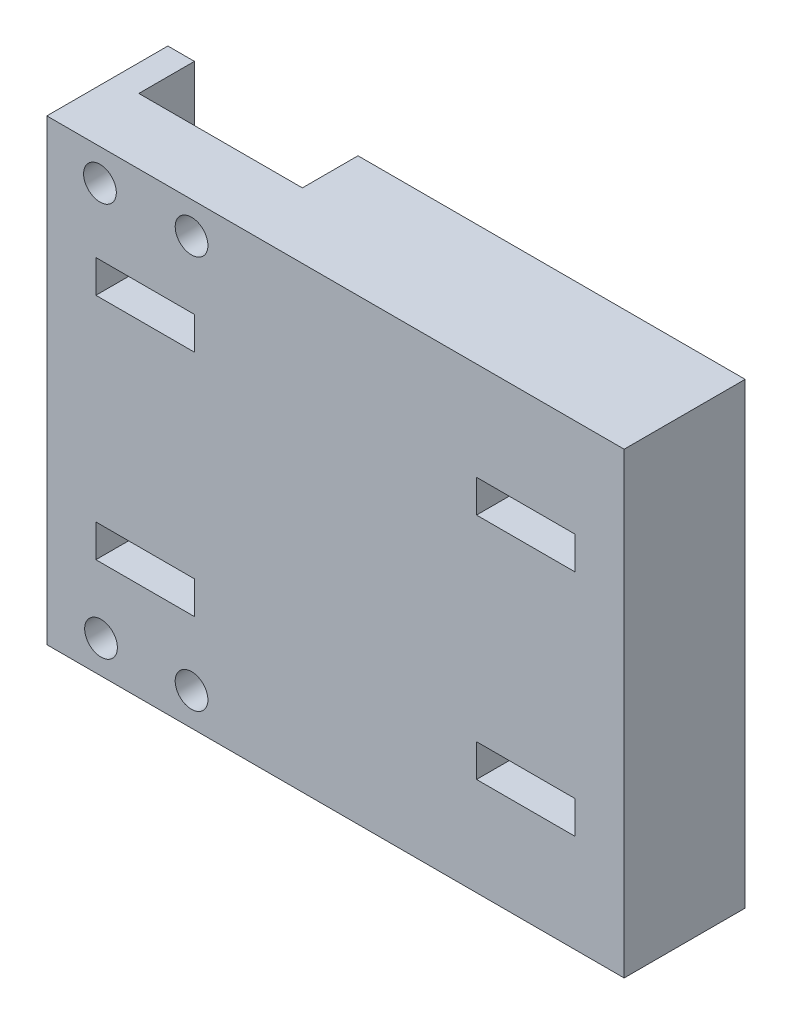
SolidWorks part; units mm, degrees
ref_plane "Front Plane" through (0, 0, 0) normal (0, 0, 1) x (1, 0, 0)
ref_plane "Top Plane" through (0, 0, 0) normal (0, 1, 0) x (1, 0, 0)
ref_plane "Right Plane" through (0, 0, 0) normal (1, 0, 0) x (0, 0, -1)
sketch "Sketch1" plane through (0, 0, 0) normal (0, 0, 1) x (1, 0, 0)
  line L1 (-43.2845, 29.3328) -> (46.7155, 29.3328)
  line L2 (-43.2845, 29.3328) -> (-43.2845, -40.6672)
  line L3 (-43.2845, -40.6672) -> (46.7155, -40.6672)
  line L4 (46.7155, 29.3328) -> (46.7155, -40.6672)
  line L5 (-38.2845, 16.8328) -> (-18.2232, 16.8328)
  line L6 (-38.2845, 16.8328) -> (-38.2845, -28.1672)
  line L7 (-38.2845, -28.1672) -> (-18.2232, -28.1672)
  line L8 (-18.2232, 16.8328) -> (-18.2232, -28.1672)
  line L9 (21.7768, 16.8328) -> (41.7155, 16.8328)
  line L10 (21.7768, 16.8328) -> (21.7768, -28.1672)
  line L11 (21.7768, -28.1672) -> (41.7155, -28.1672)
  line L12 (41.7155, 16.8328) -> (41.7155, -28.1672)
  line L13 (-35.7845, 14.3328) -> (-20.7232, 14.3328)
  line L14 (-35.7845, 14.3328) -> (-35.7845, -25.6672)
  line L15 (-35.7845, -25.6672) -> (-20.7232, -25.6672)
  line L16 (-20.7232, 14.3328) -> (-20.7232, -25.6672)
  line L17 (24.2768, 14.3328) -> (39.2155, 14.3328)
  line L18 (24.2768, 14.3328) -> (24.2768, -25.6672)
  line L19 (24.2768, -25.6672) -> (39.2155, -25.6672)
  line L20 (39.2155, 14.3328) -> (39.2155, -25.6672)
  dimension "D1" = 90
  dimension "D2" = 70
  dimension "D3" = 12.5
  dimension "D4" = 12.5
  dimension "D5" = 12.5
  dimension "D6" = 12.5
  dimension "D7" = 40
  dimension "D8" = 5
  dimension "D9" = 5
  dimension "D10" = 2.5
  dimension "D11" = 2.5
  dimension "D12" = 2.5
  dimension "D13" = 2.5
  dimension "D14" = 2.5
  dimension "D15" = 2.5
  dimension "D16" = 2.5
  dimension "D17" = 2.5
extrude "Boss-Extrude2" add sketch "Sketch1" along normal blind 10 contours L16 L13 L14 L15 | L4 L1 L2 L3 L5 L8 L7 L6 L9 L12 L11 L10 | L18 L17 L20 L19 region at (1.7401, -5.6672, 0) region at (-28.2538, -5.6672, 0)
sketch "Sketch2" plane through (0, 0, 10) normal (0, 0, 1) x (1, 0, 0)
  line L1 (-43.2845, 29.3328) -> (46.7155, 29.3328)
  line L2 (-43.2845, 29.3328) -> (-43.2845, -40.6672)
  line L3 (-43.2845, -40.6672) -> (46.7155, -40.6672)
  line L4 (46.7155, 29.3328) -> (46.7155, -40.6672)
extrude "Boss-Extrude3" add sketch "Sketch2" along normal blind 10
sketch "Sketch4" plane through (-43.2845, 0, 0) normal (-1, 0, 0) x (0, 0, 1)
  line L0 (20, 29.3328) -> (20, -40.6672)
  line L1 (20, -40.6672) -> (18.5, -40.6672)
  line L2 (20, -40.6672) -> (0, -40.6672) construction
  line L3 (18.5, -40.6672) -> (18.5, 29.3328)
  line L4 (20, 29.3328) -> (0, 29.3328) construction
  line L5 (18.5, 29.3328) -> (20, 29.3328)
  dimension "D1" = 1.5
extrude "Cut-Extrude2" cut sketch "Sketch4" against normal blind 100.5
sketch "Sketch10" plane through (0, 0, 0) normal (0, 0, -1) x (-1, 0, 0)
  line L0 (43.2845, 29.3328) -> (-46.7155, 29.3328) construction
  line L1 (43.2845, -40.6672) -> (38.2845, -40.6672)
  line L2 (43.2845, -40.6672) -> (43.2845, 29.3328)
  line L3 (43.2845, 29.3328) -> (38.2845, 29.3328)
  line L4 (38.2845, -40.6672) -> (38.2845, 29.3328)
  line L5 (43.2845, -40.6672) -> (-46.7155, -40.6672) construction
  line L6 (-46.7155, 29.3328) -> (-41.7155, 29.3328)
  line L7 (-46.7155, 29.3328) -> (-46.7155, -40.6672)
  line L8 (-46.7155, -40.6672) -> (-41.7155, -40.6672)
  line L9 (-41.7155, 29.3328) -> (-41.7155, -40.6672)
extrude "Cut-Extrude4" cut sketch "Sketch10" against normal blind 100.5
sketch "Sketch11" plane through (-35.7845, 0, 0) normal (-1, 0, 0) x (0, 0, 1)
  line L1 (10, 14.3328) -> (0, 14.3328) construction
  line L2 (0, 14.3328) -> (0, -25.6672) construction
  line L4 (3.5, 14.3328) -> (2, 14.3328)
  line L5 (3.5, 14.3328) -> (3.5, 9.3328)
  line L6 (3.5, 9.3328) -> (10, 9.3328)
  line L7 (10, 14.3328) -> (10, -25.6672) construction
  line L8 (10, 9.3328) -> (10, -20.6672)
  line L9 (10, -20.6672) -> (3.5, -20.6672)
  line L10 (3.5, -20.6672) -> (3.5, -25.6672)
  line L11 (10, -25.6672) -> (0, -25.6672) construction
  line L12 (2, 14.3328) -> (0, 9.3328)
  line L13 (0, 9.3328) -> (0, -20.6672)
  line L14 (0, -20.6672) -> (0, 10.3328)
  line L15 (0, 10.3328) -> (0, -20.6672)
  line L16 (10, 16.8328) -> (10, -28.1672) construction
  line L17 (0, 10.3328) -> (0, -20.6672)
  line L18 (0, -20.6672) -> (2, -25.6672)
  line L19 (2, -25.6672) -> (3.5, -25.6672)
  line M6 (0, 14.3328) -> (0, -25.6672)
  line M7 (0, -25.6672) -> (10, -25.6672)
  line M8 (10, -25.6672) -> (10, 14.3328)
  line M9 (10, 14.3328) -> (0, 14.3328)
  dimension "D1" = 6.5
  dimension "D2" = 6.5
  dimension "D3" = 1.5
  dimension "D4" = 1.5
  dimension "D5" = 5
  dimension "D6" = 5
  dimension "D7" = 3.5
  dimension "D8" = 5
extrude "Cut-Extrude5" cut sketch "Sketch11" against normal blind 100.5 contours L12 M9 M6 | L5 L6 M8 M9 | L9 L10 M7 M8 | L18 M6 M7 region at (-35.7845, 11.8328, 6.75) region at (-35.7845, 12.6662, 0.6667) region at (-35.7845, -24.0005, 0.6667) region at (-35.7845, -23.1672, 6.75)
sketch "Sketch12" plane through (41.7155, 0, 0) normal (1, 0, 0) x (0, 0, -1)
  line L1 (-18.5, 29.3328) -> (0, 29.3328)
  line L2 (-18.5, 29.3328) -> (-18.5, -40.6672)
  line L3 (-18.5, -40.6672) -> (0, -40.6672)
  line L4 (0, 29.3328) -> (0, -40.6672)
extrude "Boss-Extrude5" add sketch "Sketch12" along normal blind 5
sketch "Sketch13" plane through (-38.2845, 0, 0) normal (-1, 0, 0) x (0, 0, 1)
  line L1 (0, 29.3328) -> (18.5, 29.3328)
  line L2 (0, 29.3328) -> (0, -40.6672)
  line L3 (0, -40.6672) -> (18.5, -40.6672)
  line L4 (18.5, 29.3328) -> (18.5, -40.6672)
extrude "Boss-Extrude6" add sketch "Sketch13" along normal blind 5
sketch "Sketch14" plane through (0, 0, 0) normal (0, 0, -1) x (-1, 0, 0)
  line L1 (-21.7768, 16.8328) -> (18.2232, 16.8328)
  line L2 (-21.7768, 16.8328) -> (-21.7768, -28.1672)
  line L3 (-21.7768, -28.1672) -> (18.2232, -28.1672)
  line L4 (18.2232, 16.8328) -> (18.2232, -28.1672)
extrude "Boss-Extrude7" add sketch "Sketch14" against normal blind 11
sketch "Sketch15" plane through (0, 0, 18.5) normal (0, 0, 1) x (1, 0, 0)
  line L0 (-43.2845, -40.6672) -> (-43.2845, 29.3328) construction
  line L3 (46.7155, 29.3328) -> (-43.2845, 29.3328) construction
  circle A0 centre (8.7155, 24.4828) radius 2.5
  circle A1 centre (-5.2845, 24.4828) radius 2.5
  circle A2 centre (1.7155, -35.6672) radius 2.5
  dimension "D1" = 5
  dimension "D2" = 5
  dimension "D3" = 5
  dimension "D4" = 7
  dimension "D5" = 7
  dimension "D6" = 38
  dimension "D7" = 65
  dimension "D8" = 60.15
  dimension "D9" = 60.15
extrude "Cut-Extrude6" cut sketch "Sketch15" against normal blind 3
sketch "Sketch16" plane through (0, 0, 0) normal (0, 0, -1) x (-1, 0, 0)
  line L0 (-21.7768, 16.8328) -> (-21.7768, -28.1672) construction
  line L1 (-16.7768, 27.3328) -> (13.2232, 27.3328)
  line L2 (-16.7768, 27.3328) -> (-16.7768, -38.6672)
  line L3 (-16.7768, -38.6672) -> (13.2232, -38.6672)
  line L4 (13.2232, 27.3328) -> (13.2232, -38.6672)
  line L5 (18.2232, 16.8328) -> (18.2232, -28.1672) construction
  line L6 (43.2845, 29.3328) -> (-46.7155, 29.3328) construction
  line L7 (43.2845, -40.6672) -> (-46.7155, -40.6672) construction
  dimension "D1" = 5
  dimension "D2" = 5
  dimension "D3" = 2
  dimension "D4" = 2
extrude "Cut-Extrude8" cut sketch "Sketch16" against normal blind 15.5
sketch "Sketch17" plane through (0, 0, 0) normal (0, 0, -1) x (-1, 0, 0)
  line L0 (-39.2155, 9.3328) -> (-39.2155, -20.6672) construction
  line L1 (-39.2155, 1.8328) -> (-24.2768, 1.8328)
  line L2 (-39.2155, 1.8328) -> (-39.2155, -13.1672)
  line L3 (-39.2155, -13.1672) -> (-24.2768, -13.1672)
  line L4 (-24.2768, 1.8328) -> (-24.2768, -13.1672)
  line L5 (-24.2768, 9.3328) -> (-24.2768, -20.6672) construction
  line L6 (20.7232, 9.3328) -> (20.7232, -20.6672) construction
  line L7 (20.7232, 1.8328) -> (35.7845, 1.8328)
  line L8 (20.7232, 1.8328) -> (20.7232, -13.1672)
  line L9 (20.7232, -13.1672) -> (35.7845, -13.1672)
  line L10 (35.7845, 1.8328) -> (35.7845, -13.1672)
  line L11 (35.7845, 9.3328) -> (35.7845, -20.6672) construction
  line L12 (-24.2768, 9.3328) -> (-39.2155, 9.3328) construction
  line L14 (20.7232, 9.3328) -> (35.7845, 9.3328) construction
  line L15 (20.7232, -20.6672) -> (35.7845, -20.6672) construction
  dimension "D1" = 14.9387
  dimension "D2" = 15
  dimension "D3" = 7.5
  dimension "D4" = 7.5
  dimension "D5" = 7.5
extrude "Cut-Extrude10" cut sketch "Sketch17" against normal blind 10
sketch "Sketch18" plane through (0, 0, 10) normal (0, 0, -1) x (-1, 0, 0)
  line L0 (-39.2155, 9.3328) -> (-39.2155, 14.3328) construction
  line L1 (-24.2768, 9.3328) -> (-39.2155, 9.3328)
  line L2 (-24.2768, 9.3328) -> (-24.2768, 14.3328)
  line L3 (-24.2768, 14.3328) -> (-39.2155, 14.3328)
  line L4 (-39.2155, 9.3328) -> (-39.2155, 14.3328)
  line L5 (35.7845, 14.3328) -> (35.7845, 9.3328) construction
  line L6 (-39.2155, -20.6672) -> (-24.2768, -20.6672)
  line L7 (-39.2155, -20.6672) -> (-39.2155, -25.6672)
  line L8 (-39.2155, -25.6672) -> (-24.2768, -25.6672)
  line L9 (-24.2768, -20.6672) -> (-24.2768, -25.6672)
  line L10 (20.7232, -20.6672) -> (35.7845, -20.6672)
  line L11 (20.7232, -20.6672) -> (20.7232, -25.6672)
  line L12 (20.7232, -25.6672) -> (35.7845, -25.6672)
  line L13 (35.7845, -20.6672) -> (35.7845, -25.6672)
  line L14 (20.7232, 9.3328) -> (35.7845, 9.3328)
  line L15 (20.7232, 9.3328) -> (20.7232, 14.3328)
  line L16 (20.7232, 14.3328) -> (35.7845, 14.3328)
  line L17 (35.7845, 9.3328) -> (35.7845, 14.3328)
extrude "Cut-Extrude11" cut sketch "Sketch18" against normal blind 10
sketch "Sketch19" plane through (0, 0, 0) normal (0, 0, -1) x (-1, 0, 0)
  line L0 (-24.2768, 14.3328) -> (-39.2155, 14.3328) construction
  line L1 (-33.2155, 14.3328) -> (-30.2768, 14.3328)
  line L2 (-33.2155, 14.3328) -> (-33.2155, 1.8328)
  line L4 (-30.2768, 14.3328) -> (-30.2768, 1.8328)
  line L5 (-24.2768, 1.8328) -> (-39.2155, 1.8328) construction
  line L11 (35.7845, 9.3328) -> (35.7845, 1.8328) construction
  line L12 (20.7232, 1.8328) -> (35.7845, 1.8328)
  line L13 (20.7232, 1.8328) -> (20.7232, 4.8328)
  line L14 (20.7232, 4.8328) -> (35.7845, 4.8328)
  line L15 (35.7845, 1.8328) -> (35.7845, 4.8328)
  line L16 (35.7845, 14.3328) -> (20.7232, 14.3328) construction
  line L17 (26.7232, 1.8328) -> (29.7845, 1.8328)
  line L18 (26.7232, 1.8328) -> (26.7232, 14.3328)
  line L19 (26.7232, 14.3328) -> (29.7845, 14.3328)
  line L20 (29.7845, 1.8328) -> (29.7845, 14.3328)
  line L21 (20.7232, -13.1672) -> (20.7232, -20.6672) construction
  line L26 (20.7232, -25.6672) -> (35.7845, -25.6672) construction
  line L28 (26.7232, -13.1672) -> (26.7232, -25.6672)
  line L29 (26.7232, -25.6672) -> (29.7845, -25.6672)
  line L30 (29.7845, -13.1672) -> (29.7845, -25.6672)
  line L31 (-24.2768, -13.1672) -> (-24.2768, -20.6672) construction
  line L32 (-39.2155, -13.1672) -> (-24.2768, -13.1672)
  line L33 (-39.2155, -13.1672) -> (-39.2155, -16.1672)
  line L34 (-39.2155, -16.1672) -> (-24.2768, -16.1672)
  line L35 (-24.2768, -13.1672) -> (-24.2768, -16.1672)
  line L36 (-39.2155, -25.6672) -> (-24.2768, -25.6672) construction
  line L37 (-33.2155, -13.1672) -> (-30.2768, -13.1672)
  line L38 (-33.2155, -13.1672) -> (-33.2155, -25.6672)
  line L39 (-33.2155, -25.6672) -> (-30.2768, -25.6672)
  line L40 (-30.2768, -13.1672) -> (-30.2768, -25.6672)
  line L41 (-39.2155, -13.1672) -> (-39.2155, -20.6672) construction
  line L42 (-24.2768, -13.1672) -> (-24.2768, -20.6672) construction
  line L49 (35.7845, -13.1672) -> (35.7845, -20.6672) construction
  line L51 (20.7232, 9.3328) -> (20.7232, 1.8328) construction
  line L52 (20.7232, -13.1672) -> (35.7845, -13.1672)
  line L53 (20.7232, -13.1672) -> (20.7232, -16.1672)
  line L54 (20.7232, -16.1672) -> (35.7845, -16.1672)
  line L55 (35.7845, -13.1672) -> (35.7845, -16.1672)
  line L56 (35.7845, 9.3328) -> (35.7845, 1.8328) construction
  line L57 (-39.2155, 9.3328) -> (-39.2155, 1.8328) construction
  line L58 (-24.2768, 1.8328) -> (-39.2155, 1.8328)
  line L59 (-24.2768, 1.8328) -> (-24.2768, 4.8328)
  line L60 (-24.2768, 4.8328) -> (-39.2155, 4.8328)
  line L61 (-39.2155, 1.8328) -> (-39.2155, 4.8328)
  line L62 (-39.2155, 14.3328) -> (-39.2155, 9.3328) construction
  line L63 (-24.2768, 9.3328) -> (-24.2768, 1.8328) construction
  line M24 (20.7232, 9.3328) -> (20.7232, 1.8328)
  line M25 (20.7232, 1.8328) -> (35.7845, 1.8328)
  line M26 (35.7845, 1.8328) -> (35.7845, 9.3328)
  line M27 (35.7845, 9.3328) -> (20.7232, 9.3328)
  dimension "D1" = 3
  dimension "D2" = 6
  dimension "D3" = 6
  dimension "D4" = 6
  dimension "D5" = 6
  dimension "D6" = 3
  dimension "D7" = 3
  dimension "D8" = 6
  dimension "D9" = 6
  dimension "D10" = 3
  dimension "D11" = 6
  dimension "D12" = 6
extrude "Cut-Extrude12" cut sketch "Sketch19" against normal blind 10 contours L4 L60 L2 L58 | L61 L58 L2 L60 | L59 L60 L4 L58 | L60 L4 L1 L2 | L32 L40 L34 L35 | L38 L32 L33 L34 | L54 L28 L29 L30 | L53 L54 L28 L52 | L55 L52 L30 L54 | L28 L54 L30 L52 | L18 L14 M25 M24 | L12 L20 L14 L18 | L20 L14 M25 M26 | L20 L19 L18 M27 | L40 L39 L38 L37 | L20 L19 L18 L17 region at (31.7462, 9.5828, 0) region at (31.7462, 3.3328, 0) region at (36.2155, 3.3328, 0) region at (27.2768, 3.3328, 0) region at (-23.7232, 3.3328, 0) region at (-28.2538, 3.3328, 0) region at (-32.7845, 3.3328, 0) region at (-28.2538, 11.8328, 0) region at (-28.2538, -14.6672, 0) region at (-23.7232, -14.6672, 0) region at (-28.2538, -20.9172, 0) region at (-32.7845, -14.6672, 0) region at (36.2155, -14.6672, 0) region at (27.2768, -14.6672, 0)
sketch "Sketch23" plane through (0, 0, 0) normal (0, 0, -1) x (-1, 0, 0)
  line L0 (-39.2155, 14.3328) -> (-33.2155, 14.3328) construction
  line L1 (-39.2155, -25.6672) -> (-38.8655, -25.6672)
  line L2 (-39.2155, -25.6672) -> (-39.2155, 14.3328)
  line L3 (-39.2155, 14.3328) -> (-38.8655, 14.3328)
  line L4 (-38.8655, -25.1672) -> (-38.8655, 13.8328)
  line L5 (-30.2768, -25.6672) -> (-24.2768, -25.6672) construction
  line L6 (-33.2155, -25.6672) -> (-33.5655, -25.6672)
  line L7 (-33.2155, -25.1672) -> (-33.2155, 13.8328)
  line L8 (-33.2155, 14.3328) -> (-33.5655, 14.3328)
  line L9 (-33.5655, -25.1672) -> (-33.5655, 13.8328)
  line L10 (-30.2768, 14.3328) -> (-29.9268, 14.3328)
  line L11 (-30.2768, 13.8328) -> (-30.2768, -25.1672)
  line L12 (-30.2768, -25.6672) -> (-29.9268, -25.6672)
  line L13 (-29.9268, 13.8328) -> (-29.9268, -25.1672)
  line L14 (-30.2768, 14.3328) -> (-24.2768, 14.3328) construction
  line L15 (-24.2768, -25.6672) -> (-24.6268, -25.6672)
  line L16 (-24.2768, -25.6672) -> (-24.2768, 14.3328)
  line L17 (-24.2768, 14.3328) -> (-24.6268, 14.3328)
  line L18 (-24.6268, -25.1672) -> (-24.6268, 13.8328)
  line L19 (20.7232, 14.3328) -> (26.7232, 14.3328) construction
  line L20 (20.7232, -25.6672) -> (21.0732, -25.6672)
  line L21 (20.7232, -25.6672) -> (20.7232, 14.3328)
  line L22 (20.7232, 14.3328) -> (21.0732, 14.3328)
  line L23 (21.0732, -25.1672) -> (21.0732, 13.8328)
  line L24 (20.7232, -25.6672) -> (35.7845, -25.6672) construction
  line L25 (26.7232, 14.3328) -> (26.3732, 14.3328)
  line L26 (26.7232, 13.8328) -> (26.7232, -25.1672)
  line L27 (26.7232, -25.6672) -> (26.3732, -25.6672)
  line L28 (26.3732, 13.8328) -> (26.3732, -25.1672)
  line L29 (35.7845, 14.3328) -> (20.7232, 14.3328) construction
  line L30 (29.7845, -25.6672) -> (30.1345, -25.6672)
  line L31 (29.7845, -25.1672) -> (29.7845, 13.8328)
  line L32 (29.7845, 14.3328) -> (30.1345, 14.3328)
  line L33 (30.1345, -25.1672) -> (30.1345, 13.8328)
  line L34 (29.7845, -25.6672) -> (35.7845, -25.6672) construction
  line L35 (35.7845, 14.3328) -> (35.4345, 14.3328)
  line L36 (35.7845, 14.3328) -> (35.7845, -25.6672)
  line L37 (35.7845, -25.6672) -> (35.4345, -25.6672)
  line L38 (35.4345, 13.8328) -> (35.4345, -25.1672)
  line L39 (26.7232, -25.1672) -> (29.7845, -25.1672)
  line L40 (-39.2155, 14.3328) -> (-24.2768, 14.3328)
  line L41 (-39.2155, 14.3328) -> (-39.2155, 13.8328)
  line L42 (-38.8655, 13.8328) -> (-33.5655, 13.8328)
  line L43 (-24.2768, 14.3328) -> (-24.2768, 13.8328)
  line L44 (-39.2155, -25.6672) -> (-24.2768, -25.6672)
  line L45 (-39.2155, -25.6672) -> (-39.2155, -25.1672)
  line L46 (-38.8655, -25.1672) -> (-33.5655, -25.1672)
  line L47 (-24.2768, -25.6672) -> (-24.2768, -25.1672)
  line L48 (20.7232, 14.3328) -> (35.7845, 14.3328)
  line L49 (20.7232, 14.3328) -> (20.7232, 13.8328)
  line L50 (20.7232, 13.8328) -> (26.3732, 13.8328)
  line L51 (35.7845, 14.3328) -> (35.7845, 13.8328)
  line L52 (20.7232, -25.6672) -> (35.7845, -25.6672)
  line L53 (20.7232, -25.6672) -> (20.7232, -25.1672)
  line L54 (21.0732, -25.1672) -> (26.3732, -25.1672)
  line L55 (35.7845, -25.6672) -> (35.7845, -25.1672)
  line L56 (30.1345, -25.1672) -> (35.4345, -25.1672)
  line L57 (26.7232, 13.8328) -> (29.7845, 13.8328)
  line L58 (30.1345, 13.8328) -> (35.4345, 13.8328)
  line L59 (-33.2155, 13.8328) -> (-30.2768, 13.8328)
  line L60 (-29.9268, 13.8328) -> (-24.6268, 13.8328)
  line L61 (-33.2155, -25.1672) -> (-30.2768, -25.1672)
  line L62 (-29.9268, -25.1672) -> (-24.6268, -25.1672)
  line M25 (-39.2155, 4.8328) -> (-33.2155, 4.8328)
  line M26 (-33.2155, 4.8328) -> (-33.2155, 9.3328)
  line M27 (-33.2155, 9.3328) -> (-39.2155, 9.3328)
  line M28 (-39.2155, 9.3328) -> (-39.2155, 4.8328)
  dimension "D1" = 0.35
  dimension "D2" = 0.35
  dimension "D3" = 0.35
  dimension "D4" = 0.35
  dimension "D5" = 0.35
  dimension "D6" = 0.35
  dimension "D7" = 0.35
  dimension "D8" = 0.35
  dimension "D9" = 0.5
  dimension "D10" = 0.5
  dimension "D11" = 0.5
  dimension "D12" = 0.5
extrude "Cut-Extrude14" cut sketch "Sketch23" against normal blind 10 contours L61 L7 L9 L46 L4 L2 L1 L44 L6 L12 L15 L16 L17 L40 L10 L8 L3 L42 L59 L11 L62 L13 L60 L18 M25 M27 | L9 M25 M26 M27 | L4 M25 M27 M28 | L54 L23 L21 L20 L52 L27 L30 L37 L36 L35 L48 L32 L25 L22 L50 L28 L26 L57 L31 L39 L33 L58 L38 L56 region at (38.7886, -25.4172, 0) region at (39.0405, 7.0828, 0) region at (33.3905, 7.0828, 0) region at (-21.1506, -25.4172, 0)
sketch "Sketch28" plane through (46.7155, 0, 0) normal (1, 0, 0) x (0, 0, -1)
  line L0 (-18.5, 29.3328) -> (-18.5, -40.6672) construction
  line L1 (0, 16.8328) -> (-18.5, 16.8328)
  line L2 (0, 16.8328) -> (0, -27.201)
  line L3 (0, -27.201) -> (-18.5, -27.201)
  line L4 (-18.5, 16.8328) -> (-18.5, -27.201)
extrude "Cut-Extrude15" cut sketch "Sketch28" against normal blind 6
sketch "Sketch29" plane through (38.8655, 0, 0) normal (1, 0, 0) x (0, 0, -1)
  line L0 (-3.5, 9.3328) -> (-3.5, 7.7245)
  line L1 (-3.5, 7.7245) -> (-5, 7.5364)
  line L2 (-5, 7.5364) -> (-10, 8.5286)
  line L3 (-10, 16.8328) -> (-10, -27.201) construction
  line L4 (-10, 8.5286) -> (-10, 9.3328)
  line L5 (-10, 16.8328) -> (-10, -28.1672) construction
  line L6 (-10, 9.3328) -> (-3.5, 9.3328)
  line L7 (0, -5.6672) -> (-18.5, -5.6672) construction
  line L8 (0, 16.8328) -> (0, -28.1672) construction
  line L9 (-18.5, 16.8328) -> (-18.5, -27.201) construction
  line L10 (-10, -19.863) -> (-10, -20.6672)
  line L11 (-3.5, -20.6672) -> (-3.5, -19.0588)
  line L12 (-3.5, -19.0588) -> (-5, -18.8707)
  line L13 (-5, -18.8707) -> (-10, -19.863)
  line L14 (-10, -20.6672) -> (-3.5, -20.6672)
  dimension "D1" = 1.5
  dimension "D2" = 5
extrude "Cut-Extrude16" cut sketch "Sketch29" against normal blind 75
sketch "Sketch30" plane through (46.7155, 0, 0) normal (1, 0, 0) x (0, 0, -1)
  line L1 (-18.5, 16.8328) -> (0, 16.8328)
  line L2 (-18.5, 16.8328) -> (-18.5, -27.201)
  line L3 (-18.5, -27.201) -> (0, -27.201)
  line L4 (0, 16.8328) -> (0, -27.201)
extrude "Boss-Extrude9" add sketch "Sketch30" against normal blind 6
sketch "Sketch31" plane through (0, 0, 0) normal (0, 0, -1) x (-1, 0, 0)
  line L1 (-40.7155, -27.201) -> (-41.7155, -27.201)
  line L2 (-40.7155, -27.201) -> (-40.7155, -28.6141)
  line L3 (-40.7155, -28.6141) -> (-41.7155, -28.6141)
  line L4 (-41.7155, -27.201) -> (-41.7155, -28.6141)
extrude "Boss-Extrude10" add sketch "Sketch31" against normal blind 11
sketch "Sketch32" plane through (21.7768, 0, 0) normal (1, 0, 0) x (0, 0, -1)
  line L1 (-10, -28.1672) -> (-1.7534, -28.1672)
  line L2 (-10, -28.1672) -> (-10, 15.2045)
  line L3 (-10, 15.2045) -> (-1.7534, 15.2045)
  line L4 (-1.7534, -28.1672) -> (-1.7534, 15.2045)
extrude "Boss-Extrude11" add sketch "Sketch32" against normal blind 5
sketch "Sketch33" plane through (-13.2232, 0, 0) normal (1, 0, 0) x (0, 0, -1)
  line L1 (-11.4227, 12.4015) -> (-2.6112, 12.4015)
  line L2 (-11.4227, 12.4015) -> (-11.4227, -25.5179)
  line L3 (-11.4227, -25.5179) -> (-2.6112, -25.5179)
  line L4 (-2.6112, 12.4015) -> (-2.6112, -25.5179)
extrude "Boss-Extrude12" add sketch "Sketch33" against normal blind 5
sketch "Sketch34" plane through (0, 0, 0) normal (0, 0, -1) x (-1, 0, 0)
  line L0 (43.2845, -40.6672) -> (-46.7155, -40.6672) construction
  line L1 (13.2232, -40.6672) -> (-46.7155, -40.6672)
  line L2 (13.2232, -40.6672) -> (13.2232, 29.3328)
  line L3 (13.2232, 29.3328) -> (-46.7155, 29.3328)
  line L4 (-46.7155, -40.6672) -> (-46.7155, 29.3328)
  line L5 (13.2232, -38.6672) -> (13.2232, 27.3328) construction
  dimension "D1" = 0
extrude "Cut-Extrude18" cut sketch "Sketch34" against normal blind 37
sketch "Sketch35" plane through (0, 0, 0) normal (0, 0, -1) x (-1, 0, 0)
  line L0 (35.4345, -20.6672) -> (35.4345, -25.1672) construction
  line L4 (35.4345, -25.1672) -> (35.4345, -23.1672)
  line L5 (21.0732, 9.3328) -> (21.0732, 13.8328) construction
  line L6 (35.4345, 13.8328) -> (21.0732, 13.8328)
  line L7 (35.4345, 13.8328) -> (35.4345, 11.8328)
  line L8 (35.4345, 11.8328) -> (21.0732, 11.8328)
  line L9 (21.0732, 13.8328) -> (21.0732, 11.8328)
  dimension "D1" = 2
extrude "Cut-Extrude20" cut sketch "Sketch35" against normal blind 7 contours L6 L9 L8 L7 region at (-28.2538, 12.8328, 0)
sketch "Sketch36" plane through (0, 0, 0) normal (0, 0, -1) x (-1, 0, 0)
  line L0 (26.3732, 9.3328) -> (26.3732, 4.8328) construction
  line L1 (21.0732, 4.8328) -> (26.3732, 4.8328)
  line L2 (21.0732, 4.8328) -> (21.0732, 6.8328)
  line L3 (21.0732, 6.8328) -> (26.3732, 6.8328)
  line L4 (26.3732, 4.8328) -> (26.3732, 6.8328)
  line L5 (35.4345, 9.3328) -> (35.4345, 4.8328) construction
  line L6 (30.1345, 4.8328) -> (35.4345, 4.8328)
  line L7 (30.1345, 4.8328) -> (30.1345, 6.8328)
  line L8 (30.1345, 6.8328) -> (35.4345, 6.8328)
  line L9 (35.4345, 4.8328) -> (35.4345, 6.8328)
  dimension "D1" = 2
  dimension "D2" = 2
extrude "Cut-Extrude21" cut sketch "Sketch36" against normal blind 10
sketch "Sketch37" plane through (0, 0, 0) normal (0, 0, -1) x (-1, 0, 0)
  line L0 (35.4345, -16.1672) -> (35.4345, -20.6672) construction
  line L1 (21.0732, -16.1672) -> (35.4345, -16.1672)
  line L2 (21.0732, -16.1672) -> (21.0732, -17.6672)
  line L3 (21.0732, -17.6672) -> (35.4345, -17.6672)
  line L4 (35.4345, -16.1672) -> (35.4345, -17.6672)
  dimension "D1" = 1.5
extrude "Cut-Extrude22" cut sketch "Sketch37" against normal blind 10
sketch "Sketch38" plane through (-21.0732, 0, 0) normal (1, 0, 0) x (0, 0, -1)
  line L0 (-3.5, 11.8328) -> (-1, 11.8328) construction
  line L1 (-3.5, 11.8328) -> (-2, 11.8328)
  line L2 (-3.5, 11.8328) -> (-3.5, 7.8328)
  line L3 (-3.5, 7.8328) -> (-2, 7.8328)
  line L4 (-2, 11.8328) -> (-2, 7.8328)
  line L5 (-3.5, 7.7245) -> (-3.5, 11.8328) construction
  dimension "D1" = 0
  dimension "D2" = 0
  dimension "D3" = 1.5
  dimension "D4" = 4
extrude "Cut-Extrude23" cut sketch "Sketch38" against normal blind 15
sketch "Sketch39" plane through (-30.1345, 0, 0) normal (1, 0, 0) x (0, 0, -1)
  line L0 (-3.5, -25.1672) -> (-3.5, -19.0588) construction
  line L1 (-3.5, -19.0588) -> (-2, -19.0588)
  line L2 (-3.5, -19.0588) -> (-3.5, -21.0588)
  line L3 (-3.5, -21.0588) -> (-2, -21.0588)
  line L4 (-2, -19.0588) -> (-2, -21.0588)
  dimension "D1" = 0
  dimension "D2" = 0
  dimension "D3" = 2
  dimension "D4" = 1.5
extrude "Cut-Extrude24" cut sketch "Sketch39" against normal blind 6 and the other way blind 10
sketch "Sketch40" plane through (-26.3732, 0, 0) normal (-1, 0, 0) x (0, 0, 1)
  line L0 (2, -21.0588) -> (3.5, -22.4963)
  line L1 (3.5, -22.4963) -> (3.5, -21.0588)
  line L2 (3.5, -21.0588) -> (2, -21.0588)
  line L3 (2, -21.0588) -> (3.5, -21.0588) construction
  line L4 (3.5, -21.0588) -> (3.5, -25.1672) construction
  dimension "D1" = 0
  dimension "D2" = 0
  dimension "D3" = 0
extrude "Cut-Extrude26" cut sketch "Sketch40" against normal blind 6 and the other way blind 10
sketch "Sketch41" plane through (-43.2845, 0, 0) normal (-1, 0, 0) x (0, 0, 1)
  line L0 (0, 29.3328) -> (0, -40.6672) construction
  line L1 (0, 19.4988) -> (16.3977, 19.4988)
  line L2 (0, 19.4988) -> (0, -31.9251)
  line L3 (0, -31.9251) -> (16.3977, -31.9251)
  line L4 (16.3977, 19.4988) -> (16.3977, -31.9251)
extrude "Cut-Extrude27" cut sketch "Sketch41" against normal blind 5
sketch "Sketch42" plane through (-35.4345, 0, 0) normal (-1, 0, 0) x (0, 0, 1)
  line L0 (10, 8.5286) -> (2, 7.8328)
  line L1 (2, 7.8328) -> (2, 6.8328)
  line L2 (10, 6.8328) -> (0, 6.8328) construction
  line L3 (2, 6.8328) -> (10, 6.8328)
  line L4 (10, 6.8328) -> (10, 8.5286)
extrude "Boss-Extrude13" add sketch "Sketch42" against normal blind 14.37
fillet "Fillet4" radius 1 2 edges at (-23.7232, 7.8328, 2) (-32.7845, 7.8328, 2)
sketch "Sketch43" plane through (-35.4345, 0, 0) normal (-1, 0, 0) x (0, 0, 1)
  line L0 (10, -17.6672) -> (10, -19.863)
  line L1 (10, -19.863) -> (2, -19.0588)
  line L2 (2, -19.0588) -> (2, -17.6672)
  line L3 (10, -17.6672) -> (0, -17.6672) construction
  line L4 (2, -17.6672) -> (10, -17.6672)
extrude "Boss-Extrude14" add sketch "Sketch43" against normal blind 14.37
fillet "Fillet5" radius 1 2 edges at (-23.7232, -19.0588, 2) (-32.7845, -19.0588, 2)
sketch "Sketch44" plane through (-35.4345, 0, 0) normal (-1, 0, 0) x (0, 0, 1)
  line L0 (3.5, -25.1672) -> (2.65, -25.1672)
  line L1 (3.5, -25.1672) -> (1.8, -25.1672) construction
  line L2 (2.65, -25.1672) -> (2.75, -21.7775)
  line L3 (2, -21.0588) -> (3.5, -22.4963) construction
  line L4 (2.75, -21.7775) -> (3.5, -22.4963)
  line L5 (3.5, -22.4963) -> (3.5, -25.1672)
extrude "Cut-Extrude28" cut sketch "Sketch44" against normal blind 14.37
sketch "Sketch45" plane through (0, 0, 0) normal (0, 0, -1) x (-1, 0, 0)
  line L0 (35.4345, -20.6672) -> (35.4345, -25.1672) construction
  line L1 (21.0732, -25.1672) -> (35.4345, -25.1672)
  line L2 (21.0732, -25.1672) -> (21.0732, -24.1672)
  line L3 (21.0732, -24.1672) -> (35.4345, -24.1672)
  line L4 (35.4345, -25.1672) -> (35.4345, -24.1672)
  dimension "D1" = 1
extrude "Cut-Extrude29" cut sketch "Sketch45" against normal blind 14.37
sketch "Sketch46" plane through (0, 0, 0) normal (0, 0, -1) x (-1, 0, 0)
  line L1 (38.2845, 19.4988) -> (43.2845, 19.4988)
  line L2 (38.2845, 19.4988) -> (38.2845, -31.9251)
  line L3 (38.2845, -31.9251) -> (43.2845, -31.9251)
  line L4 (43.2845, 19.4988) -> (43.2845, -31.9251)
extrude "Boss-Extrude15" add sketch "Sketch46" against normal blind 18.37
sketch "Sketch48" plane through (-43.2845, 0, 0) normal (-1, 0, 0) x (0, 0, 1)
  line L0 (0, 29.3328) -> (0, -40.6672) construction
  line L1 (0, 17.8111) -> (15.405, 17.8111)
  line L2 (0, 17.8111) -> (0, -30.436)
  line L3 (0, -30.436) -> (15.405, -30.436)
  line L4 (15.405, 17.8111) -> (15.405, -30.436)
extrude "Cut-Extrude30" cut sketch "Sketch48" against normal blind 6
sketch "Sketch52" plane through (-35.4345, 0, 0) normal (-1, 0, 0) x (0, 0, 1)
  line L0 (10, 8.5286) -> (3.7822, 7.9879)
  line L1 (10, 8.5286) -> (3.0866, 7.9274) construction
  line L2 (2.7171, 9.0735) -> (2.7171, 11.8324)
  line L3 (2.7171, 11.8324) -> (1.5, 11.8328)
  line L4 (2, 11.8328) -> (1, 11.8328) construction
  line L5 (1.5, 11.8328) -> (0, 8.2794)
  line L6 (0, 9.3328) -> (0, 6.8328) construction
  line L7 (0, 8.2794) -> (0, 5.9797)
  line L8 (0, 16.8328) -> (0, -28.1672) construction
  line L9 (0, 5.9797) -> (10, 5.9797)
  line L10 (10, 16.8328) -> (10, -28.1672) construction
  line L11 (10, 5.9797) -> (10, 8.5286)
  arc A0 (3.7822, 7.9879) -> (2.7171, 9.0735) centre (3.6968, 8.9694) cw
extrude "Boss-Extrude19" add sketch "Sketch52" against normal blind 14.36
sketch "Sketch53" plane through (-35.4345, 0, 0) normal (-1, 0, 0) x (0, 0, 1)
  line L0 (0, 5.9797) -> (0, 9.3328)
  line L1 (0, 9.3328) -> (0.5, 9.3328)
  line L2 (0.5, 9.3328) -> (1.5, 11.8328)
  line L3 (2, 11.8328) -> (1, 11.8328) construction
  line L4 (1.5, 11.8328) -> (1, 11.8328)
  line L5 (1, 11.8328) -> (0, 9.3328)
  dimension "D1" = 0.5
  dimension "D2" = 0.5
extrude "Cut-Extrude33" cut sketch "Sketch53" against normal blind 15.36 contours L1 L2 L4 L5
sketch "Sketch55" plane through (-35.4345, 0, 0) normal (-1, 0, 0) x (0, 0, 1)
  line L0 (0.5, 9.3328) -> (0, 8.2586)
  line L1 (0, 9.3328) -> (0, 5.9797) construction
  line L2 (0, 8.2586) -> (0, 9.3328)
  line L3 (0, 9.3328) -> (0.5, 9.3328)
extrude "Cut-Extrude34" cut sketch "Sketch55" against normal blind 15.36
sketch "Sketch56" plane through (0, 0, 0) normal (0, 0, -1) x (-1, 0, 0)
  line L0 (21.0732, 8.2586) -> (35.4345, 8.2586) construction
  line L1 (30.1345, 11.8328) -> (26.3732, 11.8328)
  line L2 (30.1345, 11.8328) -> (30.1345, 8.2586)
  line L3 (30.1345, 8.2586) -> (26.3732, 8.2586)
  line L4 (26.3732, 11.8328) -> (26.3732, 8.2586)
extrude "Cut-Extrude35" cut sketch "Sketch56" against normal blind 5.36
sketch "Sketch58" plane through (-35.4345, 0, 0) normal (-1, 0, 0) x (0, 0, 1)
  line L5 (1.5, 11.8328) -> (2.1464, 13.4489)
  line L7 (1.5, 11.8328) -> (2.7171, 11.8324)
  line L8 (2.1464, 13.4489) -> (2.7367, 13.4489)
  line L9 (2.7367, 13.4489) -> (2.7171, 11.8324)
extrude "Boss-Extrude23" add sketch "Sketch58" against normal blind 14.36
sketch "Sketch59" plane through (0, 0, 0) normal (0, 0, -1) x (-1, 0, 0)
  line L5 (21.0745, 13.4489) -> (35.4345, 13.4489) construction
  line L7 (26.3732, 11.8328) -> (26.3732, 13.4489)
  line L9 (30.1345, 11.8328) -> (30.1345, 13.4489)
  line L10 (30.1345, 11.8328) -> (30.1345, 9.3328) construction
  line L12 (26.3732, 11.8328) -> (26.3732, 11.4311)
  line L13 (26.3732, 9.3328) -> (26.3732, 11.8328) construction
  line L14 (26.3732, 11.4311) -> (30.1345, 11.4311)
  line L15 (30.1345, 11.4311) -> (30.1345, 11.8328)
  line L16 (30.1345, 11.8328) -> (30.1345, 13.8293)
  line L17 (30.1345, 13.8293) -> (26.3732, 13.8293)
  line L18 (26.3732, 13.8293) -> (26.3732, 13.4489)
  dimension "D1" = 0
extrude "Cut-Extrude39" cut sketch "Sketch59" against normal blind 14.36 contours L17 L18 L7 L12 L14 L15 L9 L16 region at (-28.2538, 12.6302, 0)
sketch "Sketch61" plane through (0, 0, 0) normal (0, 0, -1) x (-1, 0, 0)
  line L1 (21.0745, 5.9797) -> (20.9258, 5.9797)
  line L2 (21.0745, 5.9797) -> (21.0745, 13.579)
  line L3 (21.0745, 13.579) -> (20.9258, 13.579)
  line L4 (20.9258, 5.9797) -> (20.9258, 13.579)
extrude "Cut-Extrude41" cut sketch "Sketch61" against normal blind 10
sketch "Sketch62" plane through (-35.4345, 0, 0) normal (-1, 0, 0) x (0, 0, 1)
  line L0 (10, -17.6672) -> (0, -17.6672)
  line L1 (0, -17.6672) -> (0, -20.6672)
  line L2 (0, -20.6672) -> (1.4, -24.1672)
  line L3 (0, -20.6672) -> (1.4, -24.1672) construction
  line L4 (2.6795, -24.1672) -> (1.4, -24.1672) construction
  line L5 (1.4, -24.1672) -> (2.6795, -24.1672)
  line L6 (2.6795, -24.1672) -> (2.75, -21.7775)
  line L7 (2.75, -21.7775) -> (10, -19.863)
  line L8 (10, 16.8328) -> (10, -28.1672) construction
  line L9 (10, -17.6672) -> (10, -19.863) construction
  line L10 (10, -19.863) -> (10, -17.6672)
extrude "Cut-Extrude42" cut sketch "Sketch62" against normal blind 16
sketch "Sketch65" plane through (-35.4345, 0, 0) normal (-1, 0, 0) x (0, 0, 1)
  line L0 (0, 8.2586) -> (0, 5.9797)
  line L1 (0, 5.9797) -> (10, 5.9797)
  line L2 (10, 5.9797) -> (10, 8.5286)
  line L3 (10, 8.5286) -> (3.7822, 7.9879)
  line L5 (0, 8.2586) -> (0.5, 9.3328)
  line L6 (0.5, 9.3328) -> (2.1464, 13.4489)
  line L7 (2.1464, 13.4489) -> (2.7367, 13.4489)
  line L8 (2.7171, 11.8324) -> (2.7367, 13.4489) construction
  line L10 (2.7367, 13.4489) -> (2.7171, 9.0735)
  line L11 (18.5, -5.6672) -> (0, -5.6672) construction
  line L12 (18.5, -40.6672) -> (18.5, 29.3328) construction
  line L13 (0, 16.8328) -> (0, -28.1672) construction
  line L14 (0, -5.6672) -> (18.5, -5.6672) construction
  line L15 (10, -17.314) -> (10, -19.863)
  line L16 (10, -19.863) -> (3.7822, -19.3222)
  line L17 (0, -17.314) -> (10, -17.314)
  line L18 (2.1464, -24.7833) -> (2.7367, -24.7833)
  line L19 (2.7367, -24.7833) -> (2.7171, -20.4078)
  line L20 (0.5, -20.6672) -> (2.1464, -24.7833)
  line L21 (0, -19.5929) -> (0.5, -20.6672)
  line L22 (0, -19.5929) -> (0, -17.314)
  arc A2 (2.7171, 9.0735) -> (3.7822, 7.9879) centre (3.798, 9.0686) ccw
  arc A3 (2.7171, -20.4078) -> (3.7822, -19.3222) centre (3.798, -20.4029) cw
extrude "Boss-Extrude24" add sketch "Sketch65" against normal blind 14.36
sketch "Sketch68" plane through (0, 0, 0) normal (0, 0, -1) x (-1, 0, 0)
  line L0 (43.2845, 29.3328) -> (58.3445, 29.3328)
  line L1 (58.3445, 29.3328) -> (58.3445, -40.6672)
  line L2 (58.3445, -40.6672) -> (43.2845, -40.6672)
  line L3 (43.2845, -40.6672) -> (43.2845, 29.3328)
  dimension "D1" = 15.06
  dimension "D2" = 70
  dimension "D3" = 70
  dimension "D4" = 15.06
extrude "Boss-Extrude28" add sketch "Sketch68" against normal blind 18.5
sketch "Sketch70" plane through (0, 0, 0) normal (0, 0, -1) x (-1, 0, 0)
  line L1 (37.2845, 17.8111) -> (43.2845, 17.8111)
  line L2 (37.2845, 17.8111) -> (37.2845, -30.436)
  line L3 (37.2845, -30.436) -> (43.2845, -30.436)
  line L4 (43.2845, 17.8111) -> (43.2845, -30.436)
extrude "Boss-Extrude29" add sketch "Sketch70" against normal blind 18.5
sketch "Sketch72" plane through (0, 0, 0) normal (0, 0, -1) x (-1, 0, 0)
  line L0 (58.3445, 27.3328) -> (42.2845, 27.3328)
  line L1 (58.3445, -40.6672) -> (58.3445, 29.3328) construction
  line L2 (42.2845, 27.3328) -> (42.2845, -38.6672)
  line L3 (42.2845, -38.6672) -> (58.3445, -38.6672)
  line L4 (58.3445, -38.6672) -> (58.3445, 27.3328)
  line L5 (37.2845, 16.8328) -> (37.2845, -28.1672) construction
  line L6 (58.3445, 29.3328) -> (13.2232, 29.3328) construction
  line L7 (58.3445, -40.6672) -> (13.2232, -40.6672) construction
  dimension "D1" = 5
  dimension "D2" = 2
  dimension "D3" = 2
extrude "Cut-Extrude44" cut sketch "Sketch72" against normal blind 16.5
sketch "Sketch75" plane through (0, 0, 0) normal (0, 0, -1) x (-1, 0, 0)
  line L0 (58.3445, 29.3328) -> (13.2232, 29.3328) construction
  line L1 (58.3445, -40.6672) -> (57.3445, -40.6672)
  line L2 (58.3445, -40.6672) -> (58.3445, 29.3328)
  line L3 (58.3445, 29.3328) -> (57.3445, 29.3328)
  line L4 (57.3445, -40.6672) -> (57.3445, 29.3328)
  dimension "D1" = 1
extrude "Cut-Extrude45" cut sketch "Sketch75" against normal blind 33.5
sketch "Sketch76" plane through (0, 0, 16.5) normal (0, 0, -1) x (-1, 0, 0)
  line L0 (57.3445, 27.3328) -> (57.3445, -38.6672) construction
  line L1 (42.2845, 27.3328) -> (42.2845, -38.6672) construction
  line L2 (57.3445, -40.6672) -> (13.2232, -40.6672) construction
  line L3 (57.3445, 29.3328) -> (13.2232, 29.3328) construction
  circle A0 centre (50.3445, 24.4828) radius 2.5
  circle A1 centre (57.3445, -35.6672) radius 2.5
  dimension "D1" = 5
  dimension "D2" = 5
  dimension "D3" = 15.06
  dimension "D4" = 5
  dimension "D5" = 4.85
  dimension "D6" = 8.06
extrude "Cut-Extrude46" cut sketch "Sketch76" against normal blind 33.5
mirror "Mirror15" about plane through (-57.3445, -40.6672, 33.5) normal (1, 0, 0) of bodies 179
sketch "Sketch77" plane through (0, 0, 16.5) normal (0, 0, -1) x (-1, 0, 0)
  circle A0 centre (79.3445, 24.4828) radius 2.5
  circle A1 centre (93.3445, 24.4828) radius 2.5
  circle A2 centre (93.1823, -35.6672) radius 2.5
  circle A3 centre (57.3445, -35.6672) radius 2.5 construction
  circle A4 centre (64.3445, 24.4828) radius 2.5 construction
  circle A5 centre (50.3445, 24.4828) radius 2.5 construction
  dimension "D2" = 5
  dimension "D3" = 15
  dimension "D4" = 5
  dimension "D5" = 14
  dimension "D7" = 5
  dimension "D8" = 60.15
  dimension "D9" = 60.15
  dimension "D1" = 0
  dimension "D6" = 14
extrude "Cut-Extrude48" cut sketch "Sketch77" along normal blind 26 and the other way blind 23
sketch "Sketch78" plane through (0, 0, 18.5) normal (0, 0, 1) x (1, 0, 0)
  line L0 (-13.2232, 29.3328) -> (-101.4657, 29.3328) construction
  line L1 (-68.1653, 29.3328) -> (-45.6301, 29.3328)
  line L2 (-68.1653, 29.3328) -> (-68.1653, -40.6672)
  line L3 (-68.1653, -40.6672) -> (-45.6301, -40.6672)
  line L4 (-45.6301, 29.3328) -> (-45.6301, -40.6672)
  line L5 (-13.2232, -40.6672) -> (-101.4657, -40.6672) construction
extrude "Boss-Extrude30" add sketch "Sketch78" against normal blind 2
sketch "Sketch79" plane through (0, 0, 16.5) normal (0, 0, -1) x (-1, 0, 0)
  line L0 (42.2845, 27.3328) -> (42.2845, -38.6672) construction
  line L1 (42.2845, 16.8328) -> (77.4045, 16.8328)
  line L2 (42.2845, 16.8328) -> (42.2845, -28.1672)
  line L3 (42.2845, -28.1672) -> (77.4045, -28.1672)
  line L4 (77.4045, 16.8328) -> (77.4045, -28.1672)
  line L5 (77.4045, 16.8328) -> (96.4657, 16.8328) construction
  dimension "D1" = 0
extrude "Boss-Extrude31" add sketch "Sketch79" along normal blind 16.5
sketch "Sketch80" plane through (0, 0, 0) normal (0, 0, -1) x (-1, 0, 0)
  line L0 (42.2845, -28.1672) -> (72.4045, -28.1672) construction
  line L1 (42.2845, 16.8328) -> (48.2845, 16.8328)
  line L2 (42.2845, 16.8328) -> (42.2845, -28.1672)
  line L3 (42.2845, -28.1672) -> (48.2845, -28.1672)
  line L4 (48.2845, 16.8328) -> (48.2845, -28.1672)
  line L5 (42.2845, -28.1672) -> (72.4045, -28.1672) construction
  line L6 (72.4045, 16.8328) -> (66.4045, 16.8328)
  line L7 (72.4045, 16.8328) -> (72.4045, -28.1672)
  line L8 (72.4045, -28.1672) -> (66.4045, -28.1672)
  line L9 (66.4045, 16.8328) -> (66.4045, -28.1672)
  dimension "D1" = 6
  dimension "D2" = 6
extrude "Cut-Extrude49" cut sketch "Sketch80" against normal blind 16.5
sketch "Sketch81" plane through (0, 0, 16.5) normal (0, 0, -1) x (-1, 0, 0)
  line L0 (42.2845, 27.3328) -> (42.2845, -38.6672) construction
  line L1 (42.2845, 27.3328) -> (72.4045, 27.3328)
  line L2 (42.2845, 27.3328) -> (42.2845, -38.6672)
  line L3 (42.2845, -38.6672) -> (72.4045, -38.6672)
  line L4 (72.4045, 27.3328) -> (72.4045, -38.6672)
  line L5 (72.4045, 27.3328) -> (42.2845, 27.3328) construction
  dimension "D1" = 0
extrude "Boss-Extrude33" add sketch "Sketch81" along normal blind 16.5
sketch "Sketch83" plane through (0, 0, 0) normal (0, 0, -1) x (-1, 0, 0)
  line L0 (101.4657, 29.3328) -> (13.2232, 29.3328) construction
  line L1 (97.4045, 29.3328) -> (72.4045, 29.3328)
  line L2 (97.4045, 29.3328) -> (97.4045, 19.3328)
  line L3 (97.4045, 19.3328) -> (72.4045, 19.3328)
  line L4 (72.4045, 29.3328) -> (72.4045, 19.3328)
  line L5 (101.4657, -40.6672) -> (13.2232, -40.6672) construction
  line L6 (97.4045, -40.6672) -> (72.4045, -40.6672)
  line L7 (97.4045, -40.6672) -> (97.4045, -30.6672)
  line L8 (97.4045, -30.6672) -> (72.4045, -30.6672)
  line L9 (72.4045, -40.6672) -> (72.4045, -30.6672)
  dimension "D1" = 10
  dimension "D2" = 10
  dimension "D3" = 25
  dimension "D4" = 5
  dimension "D5" = 25
  dimension "D6" = 0
extrude "Cut-Extrude50" cut sketch "Sketch83" against normal blind 8.5
sketch "Sketch84" plane through (0, 0, 18.5) normal (0, 0, 1) x (1, 0, 0)
  line L0 (-79.3445, 24.4828) -> (-79.3445, -40.6672) construction
  line L1 (-13.2232, -40.6672) -> (-101.4657, -40.6672) construction
  line L2 (-79.3445, -40.6672) -> (-93.1823, -35.6672) construction
  line L3 (-93.1823, -35.6672) -> (-79.3445, -35.6672) construction
  circle A0 centre (-79.3445, -35.6672) radius 2.5
  dimension "D1" = 5
extrude "Cut-Extrude51" cut sketch "Sketch84" against normal blind 18.5
